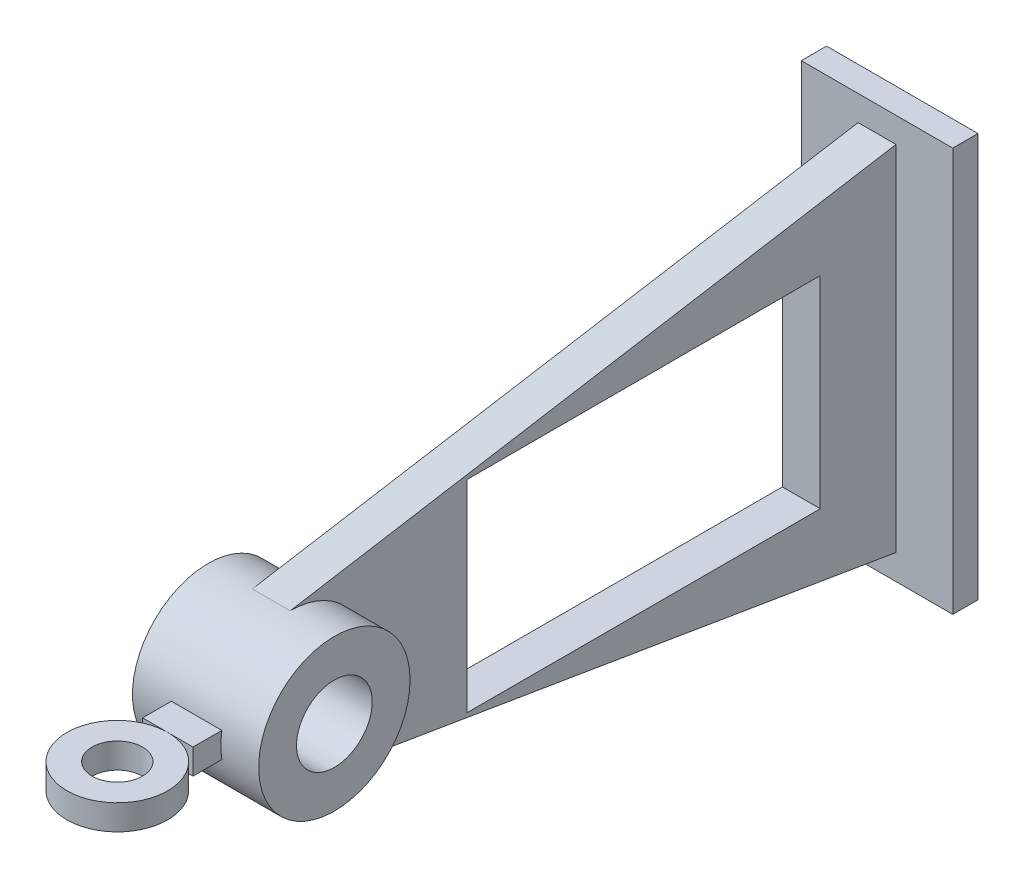
SolidWorks part; units mm, degrees
ref_plane "Front Plane" through (0, 0, 0) normal (1, 0, 0) x (0, 1, 0)
ref_plane "Top Plane" through (0, 0, 0) normal (0, 0, 1) x (0, 1, 0)
ref_plane "Right Plane" through (0, 0, 0) normal (0, 1, 0) x (-1, 0, 0)
sketch "Base Plate Sketch" plane through (0, 0, 0) normal (0, 0, 1) x (0, 1, 0)
  line L1 (-50.8, -19.05) -> (50.8, -19.05)
  line L2 (-50.8, -19.05) -> (-50.8, 19.05)
  line L3 (-50.8, 19.05) -> (50.8, 19.05)
  line L4 (50.8, -19.05) -> (50.8, 19.05)
  line L5 (-50.8, -19.05) -> (50.8, 19.05) construction
  line L6 (-50.8, 19.05) -> (50.8, -19.05) construction
  point P0 (0, 0)
extrude "Base Plate" add sketch "Base Plate Sketch" against normal blind 6.35
sketch "A-Frame Sketch" plane through (0, 0, 0) normal (1, 0, 0) x (0, 1, 0)
  line L0 (-44.45, 0) -> (44.45, 0)
  line L1 (44.45, 0) -> (19.05, 152.4)
  line L2 (19.05, 152.4) -> (-19.05, 152.4)
  line L3 (-19.05, 152.4) -> (-44.45, 0)
extrude "A-Frame Body" add sketch "A-Frame Sketch" along normal blind 4.7625 and the other way blind 4.7625
sketch "Center Cutout Sketch" plane through (0, 0, 0) normal (1, 0, 0) x (0, 1, 0)
  line L0 (-25.4, 19.05) -> (25.4, 19.05)
  line L1 (25.4, 19.05) -> (25.4, 107.95)
  line L2 (25.4, 107.95) -> (-25.4, 107.95)
  line L3 (-25.4, 107.95) -> (-25.4, 19.05)
extrude "Center Cutout" cut sketch "Center Cutout Sketch" against normal through all and the other way through all
sketch "Bearing Housing Sketch" plane through (0, 0, 0) normal (1, 0, 0) x (0, 1, 0)
  circle A0 centre (0, 152.4) radius 19.05
extrude "Bearing Housing" add sketch "Bearing Housing Sketch" along normal blind 15.875 and the other way blind 15.875
sketch "Bearing Hole Sketch" plane through (0, 0, 0) normal (1, 0, 0) x (0, 1, 0)
  circle A0 centre (0, 152.4) radius 9.525
extrude "Bearing Through-Hole" cut sketch "Bearing Hole Sketch" against normal through all and the other way through all
sketch "Mounting Holes Sketch" plane through (0, 0, 0) normal (0, 0, 1) x (0, 1, 0)
  circle A0 centre (-38.1, -9.525) radius 4.7625
  circle A1 centre (38.1, -9.525) radius 4.7625
  circle A2 centre (38.1, 9.525) radius 4.7625
  circle A3 centre (-38.1, 9.525) radius 4.7625
sketch "Eyelet Connector Sketch" plane through (0, 0, 0) normal (0, 1, 0) x (-1, 0, 0)
  line L1 (-6.35, 165.735) -> (6.35, 165.735)
  line L2 (-6.35, 165.735) -> (-6.35, 178.435)
  line L3 (-6.35, 178.435) -> (6.35, 178.435)
  line L4 (6.35, 165.735) -> (6.35, 178.435)
  line L5 (-6.35, 165.735) -> (6.35, 178.435) construction
  line L6 (-6.35, 178.435) -> (6.35, 165.735) construction
  point P0 (0, 172.085)
extrude "Eyelet Connector" add sketch "Eyelet Connector Sketch" along normal blind 3.175 and the other way blind 3.175
sketch "Eyelet Ring Sketch" plane through (0, 0, 0) normal (0, 1, 0) x (-1, 0, 0)
  circle A0 centre (0, 191.135) radius 12.7
  circle A1 centre (0, 191.135) radius 6.35
extrude "Lifting Eyelet" add sketch "Eyelet Ring Sketch" along normal blind 3.175 and the other way blind 3.175
